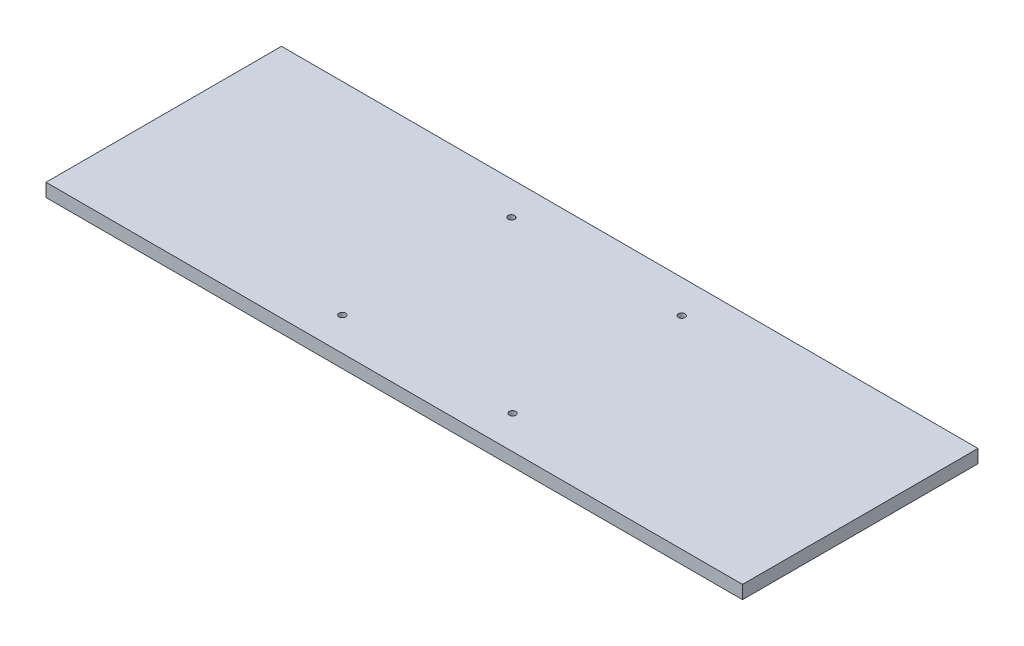
SolidWorks part; units mm, degrees
ref_plane "Front Plane" through (0, 0, 0) normal (0, 0, 1) x (1, 0, 0)
ref_plane "Top Plane" through (0, 0, 0) normal (0, 1, 0) x (1, 0, 0)
ref_plane "Right Plane" through (0, 0, 0) normal (1, 0, 0) x (0, 0, -1)
sketch "Sketch1" plane through (0, 0, 0) normal (0, 1, 0) x (1, 0, 0)
  line L1 (0, 0) -> (420, 0)
  line L2 (0, 0) -> (0, 142)
  line L3 (0, 142) -> (420, 142)
  line L4 (420, 0) -> (420, 142)
  circle A0 centre (158.6667, 20) radius 2 construction
  circle A1 centre (261.3333, 20) radius 2 construction
  circle A2 centre (261.3333, 122) radius 2 construction
  circle A3 centre (158.6667, 122) radius 2 construction
  circle A4 centre (158.6667, 20) radius 2
  circle A5 centre (261.3333, 20) radius 2
  circle A6 centre (261.3333, 122) radius 2
  circle A7 centre (158.6667, 122) radius 2
  dimension "D1" = 142
  dimension "D2" = 420
extrude "Boss-Extrude1" add sketch "Sketch1" along normal blind 8
